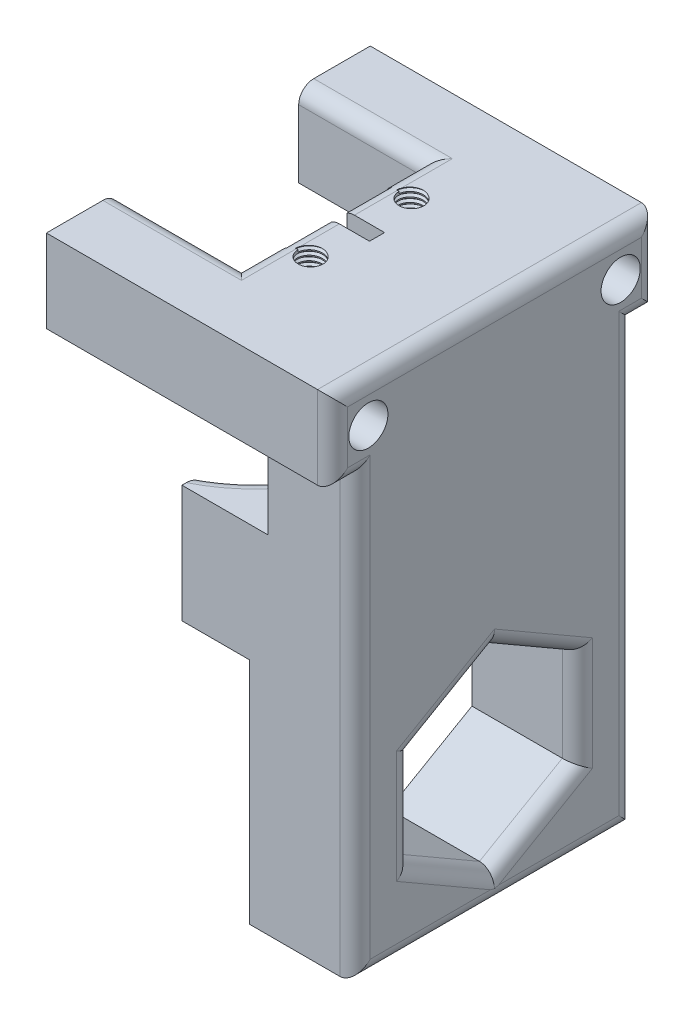
SolidWorks part; units mm, degrees
material "ABS"
ref_plane "Front Plane" through (0, 0, 0) normal (0, 0, 1) x (1, 0, 0)
ref_plane "Top Plane" through (0, 0, 0) normal (0, 1, 0) x (1, 0, 0)
ref_plane "Right Plane" through (0, 0, 0) normal (1, 0, 0) x (0, 0, -1)
sketch "Sketch2" plane through (0, 0, 0) normal (1, 0, 0) x (0, 0, -1)
  line L1 (0, 16.1312) -> (-13.97, 8.0656)
  line L2 (-13.97, 8.0656) -> (-13.97, -8.0656)
  line L3 (-13.97, -8.0656) -> (0, -16.1312)
  line L4 (0, -16.1312) -> (13.97, -8.0656)
  line L5 (13.97, -8.0656) -> (13.97, 8.0656)
  line L6 (13.97, 8.0656) -> (0, 16.1312)
  line L7 (-23.495, -21.2112) -> (23.495, -21.2112)
  line L8 (-23.495, -21.2112) -> (-23.495, 52.4488)
  line L9 (-23.495, 66.4188) -> (23.495, 66.4188)
  line L10 (23.495, -21.2112) -> (23.495, 52.4488)
  line L11 (-23.495, 66.4188) -> (-27.305, 66.4188)
  line L13 (-23.495, 52.4488) -> (-27.305, 52.4488)
  line L14 (-27.305, 66.4188) -> (-27.305, 52.4488)
  line L15 (23.495, 66.4188) -> (27.305, 66.4188)
  line L17 (23.495, 52.4488) -> (27.305, 52.4488)
  line L18 (27.305, 66.4188) -> (27.305, 52.4488)
  circle A0 centre (0, 0) radius 13.97 construction
  point P13 (0, -21.2112)
  point P20 (-25.4, 52.4488)
  dimension "D1" = 27.94
  dimension "D2" = 5.08
  dimension "D3" = 46.99
  dimension "D4" = 87.63
  dimension "D5" = 3.81
  dimension "D7" = 13.97
extrude "Boss-Extrude1" add sketch "Sketch2" along normal blind 17.78
sketch "Sketch4" plane through (0, 0, 0) normal (-1, 0, 0) x (0, 0, 1)
  line L0 (-23.495, -21.2112) -> (-23.495, 52.4488) construction
  line L1 (-23.495, 17.4012) -> (23.495, 17.4012)
  line L2 (-23.495, 17.4012) -> (-23.495, 52.4488)
  line L3 (-23.495, 66.4188) -> (23.495, 66.4188)
  line L4 (23.495, 17.4012) -> (23.495, 52.4488)
  line L5 (23.495, 52.4488) -> (23.495, -21.2112) construction
  line L6 (-27.305, 66.4188) -> (27.305, 66.4188) construction
  line L7 (27.305, 66.4188) -> (27.305, 52.4488) construction
  line L8 (27.305, 52.4488) -> (23.495, 52.4488) construction
  line L9 (-23.495, 52.4488) -> (-27.305, 52.4488) construction
  line L10 (-27.305, 52.4488) -> (-27.305, 66.4188) construction
  line L11 (27.305, 66.4188) -> (27.305, 52.4488)
  line L12 (27.305, 52.4488) -> (23.495, 52.4488)
  line L13 (-23.495, 52.4488) -> (-27.305, 52.4488)
  line L14 (-27.305, 52.4488) -> (-27.305, 66.4188)
  line L15 (-27.305, 66.4188) -> (27.305, 66.4188)
  line M5 (23.495, -21.2112) -> (23.495, 52.4488)
  line M6 (27.305, 66.4188) -> (-27.305, 66.4188)
  line M7 (-23.495, 52.4488) -> (-23.495, -21.2112)
  line M15 (23.495, 52.4488) -> (27.305, 52.4488)
  line M16 (27.305, 52.4488) -> (27.305, 66.4188)
  line M17 (-27.305, 66.4188) -> (-27.305, 52.4488)
  line M18 (-27.305, 52.4488) -> (-23.495, 52.4488)
  dimension "D1" = 1.27
extrude "Boss-Extrude2" add sketch "Sketch4" along normal blind 11.43 contours L1 M7 M5 M15 M16 M6 M17 M18 region at (0, 42.6841, 0)
sketch "Sketch5" plane through (0, 66.4188, 0) normal (0, 1, 0) x (1, 0, 0)
  line L0 (0, 0) -> (-22.7305, 0) construction
  line L2 (-11.43, -27.305) -> (-11.43, 27.305) construction
  circle A0 centre (-22.7305, 0) radius 34.925
  circle A1 centre (-22.7305, 0) radius 22.86
  dimension "D2" = 69.85
  dimension "D3" = 45.72
  dimension "D1" = 11.3005
extrude "Cut-Extrude1" cut sketch "Sketch5" against normal blind 15.24 from offset 13.97 contours A1 A0 | A1 region at (-56.6676, 66.4188, 0) region at (-22.7305, 66.4188, 0) offset against normal yes
extrude "Cut-Extrude2" cut sketch "Sketch5<3>" against normal blind 40.64 from surface contours A1 region at (-22.7305, 66.4188, 0) starting at face at (-1.8888, 37.2088, 0)
sketch "Sketch5<3>" plane through (0, 66.4188, 0) normal (0, 1, 0) x (1, 0, 0) same geometry as "Sketch5"
sketch "Sketch6" plane through (-11.43, 0, 0) normal (-1, 0, 0) x (0, 0, 1)
  line L12 (-27.305, 66.4188) -> (-27.305, 52.4488)
  line L13 (-27.305, 52.4488) -> (27.305, 52.4488)
  line L14 (27.305, 52.4488) -> (27.305, 66.4188)
  line L15 (27.305, 66.4188) -> (-27.305, 66.4188)
  line L16 (-27.305, 66.4188) -> (-27.305, 52.4488)
  line L17 (-27.305, 52.4488) -> (27.305, 52.4488)
  line L18 (27.305, 52.4488) -> (27.305, 66.4188)
  line L19 (27.305, 66.4188) -> (-27.305, 66.4188)
  dimension "D1" = 0
extrude "Boss-Extrude3" add sketch "Sketch6" along normal blind 19.05
sketch "Sketch7" plane through (0, 66.4188, 0) normal (0, 1, 0) x (1, 0, 0)
  line L0 (-30.48, -27.305) -> (-30.48, 27.305) construction
  line L1 (-30.48, 15.24) -> (-9.652, 15.24)
  line L2 (-30.48, 15.24) -> (-30.48, -15.24)
  line L3 (-30.48, -15.24) -> (-9.652, -15.24)
  line L4 (-9.652, 15.24) -> (-9.652, -15.24)
  line L6 (-9.652, -8.89) -> (-8.382, -8.89)
  line L7 (-9.652, -8.89) -> (-9.652, 8.89)
  line L8 (-9.652, 8.89) -> (-8.382, 8.89)
  line L9 (-8.382, -8.89) -> (-8.382, 8.89)
  point P6 (-9.652, 0)
  point P12 (-8.382, 0)
  line M6 (-30.48, 27.305) -> (-30.48, -27.305)
  dimension "D1" = 30.48
  dimension "D2" = 20.828
  dimension "D3" = 17.78
  dimension "D4" = 1.27
extrude "Cut-Extrude3" cut sketch "Sketch7" against normal up to surface (13.97 mm away) contours L6 L9 L8 L4 | L4 L1 L3 M6 region at (-20.066, 66.4188, 0) region at (-9.017, 66.4188, 0) up to face at (3.1831, 52.4488, 0)
sketch "Sketch8" plane through (0, 66.4188, 0) normal (0, 1, 0) x (1, 0, 0)
  line L0 (-9.652, -15.24) -> (-9.652, -8.89) construction
  line L1 (-9.652, -1.27) -> (-2.032, -1.27)
  line L2 (-9.652, -1.27) -> (-9.652, 1.27)
  line L3 (-9.652, 1.27) -> (-2.032, 1.27)
  line L4 (-2.032, -1.27) -> (-2.032, 1.27)
  point P6 (-5.842, -1.27)
  point P7 (-9.652, 0)
  dimension "D1" = 2.54
  dimension "D2" = 7.62
extrude "Cut-Extrude4" cut sketch "Sketch8" against normal blind 2.54
sketch "Sketch9" plane through (0, 66.4188, 0) normal (0, 1, 0) x (1, 0, 0)
  line L0 (17.78, 27.305) -> (17.78, -27.305) construction
  line L1 (17.78, -23.495) -> (-30.48, -23.495) construction
  line L2 (0, 0) -> (17.78, 0) construction
  circle A0 centre (-4.7193, -8.509) radius 1.27
  circle A1 centre (-4.7193, 8.509) radius 1.27
  point P0 (-4.7193, -8.509)
  point P9 (-4.7193, 8.509)
  dimension "D3" = 2.54
  dimension "D1" = 22.4993
  dimension "D2" = 14.986
hole_wizard "Tap Drill for M5x0.8 Tap1" positions "Sketch9" profile "Sketch10" hole size "M5x0.8" standard "ANSI Metric"
sketch "Sketch10" plane through (-4.7193, 66.4188, 8.509) normal (1, 0, 0) x (0, 0, 1)
  line L0 (0, 0) -> (0, 9.1358)
  line L1 (0, 9.1358) -> (2.1, 7.874)
  line L2 (2.1, 7.874) -> (2.1, 0)
  line L5 (2.1, 0) -> (0, 0)
  line L10 (0, 9.1358) -> (-2.1, 7.874) construction
  line L11 (0, -6.35) -> (0, 107.95) construction
  dimension "Hole Dia." = 4.2
  dimension "Hole Depth" = 7.874
  dimension "Drill Angle" = 118
sketch "Sketch12" plane through (-30.48, 0, 0) normal (-1, 0, 0) x (0, 0, 1)
  line L1 (-21.2725, 59.4338) -> (-21.2725, 52.4488) construction
  line L3 (-27.305, 59.4338) -> (-21.2725, 59.4338) construction
  line L5 (-21.2725, 59.4338) -> (-21.2725, 66.4188) construction
  line L7 (-21.2725, 59.4338) -> (-15.24, 59.4338) construction
  line L8 (-15.24, 52.4488) -> (-15.24, 66.4188) construction
  line L9 (0, 0) -> (0, 66.4188) construction
  line L10 (1.27, 66.4188) -> (-1.27, 66.4188) construction
  line L11 (-15.24, 66.4188) -> (-27.305, 66.4188) construction
  line L12 (-23.495, 52.4488) -> (23.495, 52.4488) construction
  line L13 (-27.305, 66.4188) -> (-27.305, 52.4488) construction
  circle A0 centre (-21.2725, 59.4338) radius 3.302
  circle A1 centre (21.2725, 59.4338) radius 3.302
  dimension "D1" = 6.604
extrude "Cut-Extrude5" cut sketch "Sketch12" against normal through all
fillet "Fillet1" radius 2.54 1 edges at (0.1295, 37.2088, 0)
fillet "Fillet3" radius 2.54 18 edges at (17.78, 12.0984, 6.985) (17.78, 0, 13.97) (17.78, -12.0984, 6.985) (17.78, -12.0984, -6.985) (17.78, 0, -13.97) (17.78, 12.0984, -6.985) (17.78, 66.4188, 0) (17.78, 15.6188, -23.495) (17.78, -21.2112, 0) (17.78, 15.6188, 23.495) (-20.066, 66.4188, 15.24) (-9.652, 66.4188, 12.065) (-9.652, 66.4188, -12.065) (-20.066, 66.4188, -15.24) (17.78, 52.4488, 25.4) (17.78, 59.4338, 27.305) (17.78, 59.4338, -27.305) (17.78, 52.4488, -25.4)
thread "Thread1" pitch 0.8 method cut profile "Thread Profile2" start angle 0, offset 0.254, length 10, pitch 0.8, diameter 4.2
ref_plane "Plane2" through (-6.8193, 66.6728, 8.509) normal (0, 0, 1) x (-1, 0, 0)
sketch "Thread Profile2" plane through (-6.8193, 66.6728, 8.509) normal (0, 0, 1) x (-1, 0, 0)
  line L0 (0, 0) -> (0, 0.8) construction
  line L1 (0, 0) -> (0.433, 0.25)
  line L2 (0.433, 0.25) -> (0.433, 0.35)
  line L3 (0.433, 0.35) -> (0, 0.6)
  line L4 (0.433, 0.3) -> (0, 0.3) construction
  line L11 (0, 0) -> (0, 0.6)
  point P2 (0, 0)
  dimension "Pitch" = 0.8
  dimension "Profile_Angle" = 60
  dimension "Profile_Land" = 0.1
  dimension "Profile_Height" = 0.433
thread "Thread2" pitch 0.8 method cut profile "Thread Profile3" start angle 0, offset 0.254, length 10, pitch 0.8, diameter 4.2
ref_plane "Plane3" through (-6.8193, 66.6728, -8.509) normal (0, 0, 1) x (-1, 0, 0)
sketch "Thread Profile3" plane through (-6.8193, 66.6728, -8.509) normal (0, 0, 1) x (-1, 0, 0)
  line L0 (0, 0) -> (0, 0.8) construction
  line L1 (0, 0) -> (0.433, 0.25)
  line L2 (0.433, 0.25) -> (0.433, 0.35)
  line L3 (0.433, 0.35) -> (0, 0.6)
  line L4 (0.433, 0.3) -> (0, 0.3) construction
  line L11 (0, 0) -> (0, 0.6)
  point P2 (0, 0)
  dimension "Pitch" = 0.8
  dimension "Profile_Angle" = 60
  dimension "Profile_Land" = 0.1
  dimension "Profile_Height" = 0.433
